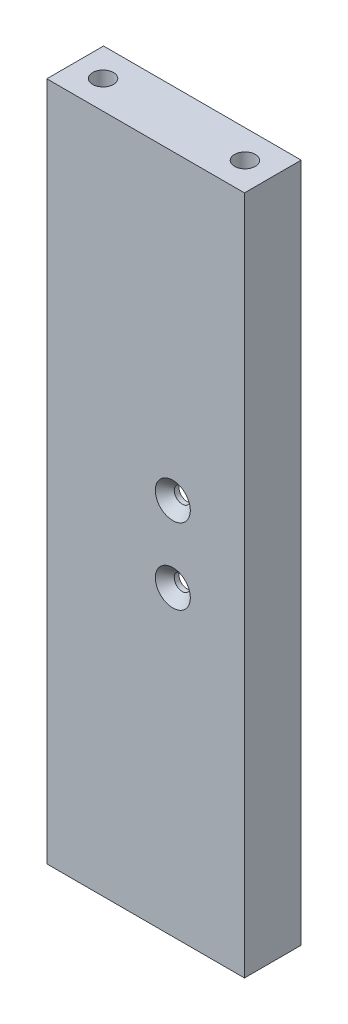
SolidWorks part; units mm, degrees
ref_plane "Front Plane" through (0, 0, 0) normal (0, 0, 1) x (1, 0, 0)
ref_plane "Top Plane" through (0, 0, 0) normal (0, 1, 0) x (1, 0, 0)
ref_plane "Right Plane" through (0, 0, 0) normal (1, 0, 0) x (0, 0, -1)
sketch "Sketch1" plane through (0, 0, 0) normal (0, 0, 1) x (1, 0, 0)
  line L1 (-20.9, 0) -> (20.9, 0)
  line L2 (-20.9, 0) -> (-20.9, 143.8)
  line L3 (-20.9, 143.8) -> (20.9, 143.8)
  line L4 (20.9, 0) -> (20.9, 143.8)
  point P4 (0, 0)
  dimension "D1" = 143.8
  dimension "D2" = 41.8
extrude "Boss-Extrude1" add sketch "Sketch1" against normal blind 12
shell "Shell1" thickness 7 removed face at (0, 71.9, -12)
sketch "Sketch2" plane through (0, 143.8, 0) normal (0, 1, 0) x (1, 0, 0)
  line L0 (0, 12) -> (0, 0) construction
  line L1 (20.9, 12) -> (-20.9, 12) construction
  line L5 (20.9, 0) -> (-20.9, 0) construction
  circle A1 centre (-15, 6) radius 2.2
  circle A2 centre (15, 6) radius 2.2
  dimension "D1" = 4.4
  dimension "D2" = 6
  dimension "D3" = 15
extrude "Cut-Extrude1" cut sketch "Sketch2" against normal blind 5.2
ref_plane "Plane1" through (0, 71.9, 0) normal (0, 1, 0) x (1, 0, 0)
mirror "Mirror1" about plane through (0, 71.9, 0) normal (0, 1, 0) of "Cut-Extrude1"
sketch "Sketch3" plane through (-20.9, 0, 0) normal (-1, 0, 0) x (0, 0, 1)
  line L0 (-6, 143.8) -> (-6, 0) construction
  line L1 (-12, 143.8) -> (0, 143.8) construction
  line L2 (-12, 0) -> (0, 0) construction
  line L3 (0, 71.9) -> (-12, 71.9) construction
  line L4 (0, 143.8) -> (0, 0) construction
  line L5 (-12, 143.8) -> (-12, 0) construction
  circle A0 centre (-6, 129.4) radius 2.2
  circle A1 centre (-6, 14.4) radius 2.2
  dimension "D1" = 57.5
  dimension "D2" = 4.4
extrude "Cut-Extrude2" cut sketch "Sketch3" against normal blind 5.2
sketch "Sketch5" plane through (0, 0, -3) normal (0, 0, -1) x (-1, 0, 0)
  line L0 (-13.9, 71.9) -> (13.9, 71.9) construction
  line L1 (-13.9, 7) -> (-13.9, 136.8) construction
  line L2 (13.9, 136.8) -> (13.9, 7) construction
  line L3 (-5.75, 63.9) -> (-5.75, 79.9) construction
  line L4 (8, 61.65) -> (-8, 61.65) construction
  line L5 (8, 61.65) -> (8, 82.15) construction
  line L6 (8, 82.15) -> (-8, 82.15) construction
  line L7 (-8, 61.65) -> (-8, 82.15) construction
  line L8 (8, 61.65) -> (-8, 82.15) construction
  line L9 (8, 82.15) -> (-8, 61.65) construction
  circle A0 centre (-5.75, 63.9) radius 1.7
  circle A1 centre (-5.75, 79.9) radius 1.7
  point P6 (0, 71.9)
  point P15 (-5.75, 71.9)
  dimension "D2" = 3.4
  dimension "D1" = 16
  dimension "D3" = 16
  dimension "D4" = 20.5
  dimension "D5" = 2.25
extrude "Cut-Extrude3" cut sketch "Sketch5" against normal blind 10
chamfer "Chamfer1" distance 2 angle 45 2 edges at (4.05, 63.9, 0) (4.05, 79.9, 0)
